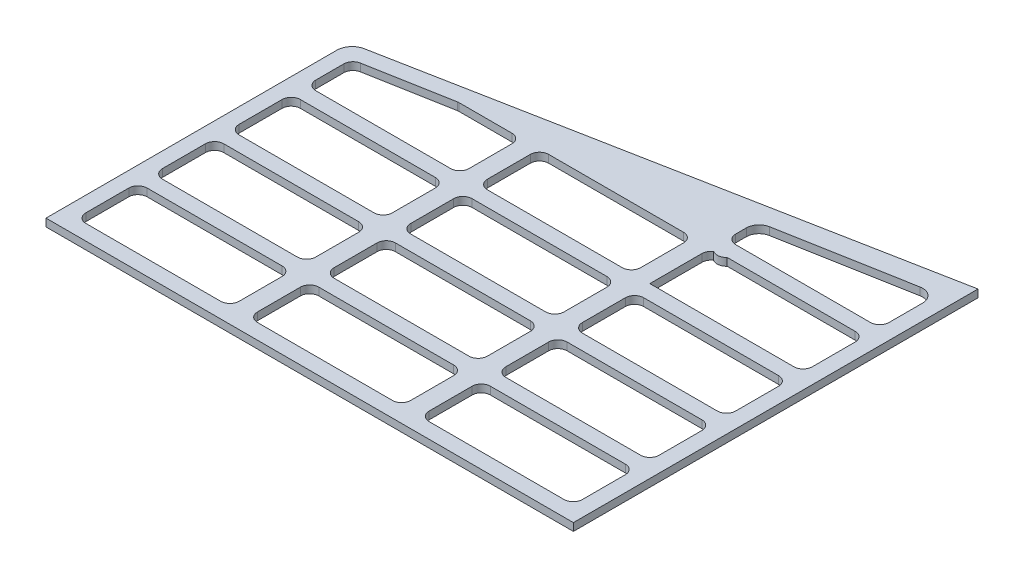
SolidWorks part; units mm, degrees
material "Balsa"
ref_plane "Front Plane" through (0, 0, 0) normal (0, 0, 1) x (1, 0, 0)
ref_plane "Top Plane" through (0, 0, 0) normal (0, 1, 0) x (1, 0, 0)
ref_plane "Right Plane" through (0, 0, 0) normal (1, 0, 0) x (0, 0, -1)
sketch "Sketch1" plane through (0, 0, 0) normal (0, 1, 0) x (1, 0, 0)
  line L0 (0, 0) -> (437.0222, 0)
  line L1 (437.0222, 335.28) -> (10.3078, 253.437)
  line L2 (0, 240.9644) -> (0, 0)
  line L3 (437.0222, 0) -> (437.0222, 335.28)
  arc A0 (10.3078, 253.437) -> (0, 240.9644) centre (12.7, 240.9644) ccw
  point P7 (0, 251.46)
  dimension "D4" = 12.7
  dimension "D1" = 251.46
  dimension "D2" = 437.0222
  dimension "D3" = 335.28
extrude "Boss-Extrude1" add sketch "Sketch1" along normal blind 6.35
sketch "Sketch2" plane through (0, 6.35, 0) normal (0, 1, 0) x (1, 0, 0)
  line L0 (0, 0) -> (437.0222, 0) construction
  line L1 (20.32, 12.7) -> (132.08, 12.7)
  line L2 (12.7, 20.32) -> (12.7, 55.88)
  line L3 (20.32, 63.5) -> (132.08, 63.5)
  line L4 (139.7, 20.32) -> (139.7, 55.88)
  line L5 (0, 240.9644) -> (0, 0) construction
  line L6 (154.94, 20.32) -> (154.94, 55.88)
  line L7 (162.56, 12.7) -> (274.32, 12.7)
  line L8 (281.94, 20.32) -> (281.94, 55.88)
  line L9 (162.56, 63.5) -> (274.32, 63.5)
  line L10 (297.18, 20.32) -> (297.18, 55.88)
  line L11 (304.8, 12.7) -> (416.56, 12.7)
  line L12 (424.18, 20.32) -> (424.18, 55.88)
  line L13 (304.8, 63.5) -> (416.56, 63.5)
  line L14 (154.94, 83.82) -> (154.94, 119.38)
  line L15 (162.56, 76.2) -> (274.32, 76.2)
  line L16 (281.94, 83.82) -> (281.94, 119.38)
  line L17 (162.56, 127) -> (274.32, 127)
  line L18 (297.18, 83.82) -> (297.18, 119.38)
  line L19 (304.8, 76.2) -> (416.56, 76.2)
  line L20 (424.18, 83.82) -> (424.18, 119.38)
  line L21 (304.8, 127) -> (416.56, 127)
  line L22 (154.94, 147.32) -> (154.94, 182.88)
  line L23 (162.56, 139.7) -> (274.32, 139.7)
  line L24 (281.94, 147.32) -> (281.94, 182.88)
  line L25 (162.56, 190.5) -> (274.32, 190.5)
  line L26 (297.18, 147.32) -> (297.18, 182.88)
  line L27 (304.8, 139.7) -> (416.56, 139.7)
  line L28 (424.18, 147.32) -> (424.18, 182.88)
  line L29 (304.8, 190.5) -> (416.56, 190.5)
  line L30 (154.94, 210.82) -> (154.94, 246.38)
  line L31 (162.56, 203.2) -> (274.32, 203.2)
  line L32 (281.94, 210.82) -> (281.94, 246.38)
  line L33 (162.56, 254) -> (274.32, 254)
  line L34 (297.18, 203.2) -> (297.18, 246.38)
  line L35 (297.18, 203.2) -> (416.56, 203.2)
  line L36 (424.18, 210.82) -> (424.18, 246.38)
  line L37 (304.8, 254) -> (416.56, 254)
  line L39 (242.4582, 266.7) -> (274.32, 266.7)
  line L40 (281.94, 274.32) -> (281.94, 280.0963)
  line L42 (297.18, 274.32) -> (297.18, 283.103)
  line L43 (310.8336, 266.7) -> (413.1927, 266.7)
  line L44 (424.18, 274.32) -> (424.18, 302.2704)
  line L46 (12.7, 83.82) -> (12.7, 119.38)
  line L47 (20.32, 76.2) -> (132.08, 76.2)
  line L48 (139.7, 83.82) -> (139.7, 119.38)
  line L49 (20.32, 127) -> (132.08, 127)
  line L50 (12.7, 147.32) -> (12.7, 182.88)
  line L51 (20.32, 139.7) -> (132.08, 139.7)
  line L52 (139.7, 147.32) -> (139.7, 182.88)
  line L53 (20.32, 190.5) -> (132.08, 190.5)
  line L54 (12.7, 210.82) -> (12.7, 234.048)
  line L55 (20.32, 203.2) -> (132.08, 203.2)
  line L56 (139.7, 210.82) -> (139.7, 246.38)
  line L57 (88.3426, 254) -> (132.08, 254)
  line L62 (411.6457, 312.7366) -> (305.9194, 293.5692)
  line L63 (272.9607, 287.5941) -> (241.0989, 281.8178)
  line L64 (12.7, 317.5) -> (139.7, 317.5) [skipped]
  line L65 (139.7, 266.7) -> (139.7, 317.5) [skipped]
  line L66 (12.7, 266.7) -> (12.7, 317.5) [skipped]
  line L67 (12.7, 266.7) -> (139.7, 266.7) [skipped]
  line L68 (154.94, 266.7) -> (154.94, 317.5) [skipped]
  line L69 (154.94, 317.5) -> (281.94, 317.5) [skipped]
  line L70 (297.18, 317.5) -> (424.18, 317.5) [skipped]
  line L71 (86.9833, 253.8778) -> (18.9607, 241.5458)
  line L72 (310.8336, 266.7) -> (297.18, 266.7)
  line L73 (304.8, 266.7) -> (416.56, 266.7)
  arc A0 (241.0989, 281.8178) -> (242.4582, 266.7) centre (242.4582, 274.32) ccw
  arc A1 (281.94, 280.0963) -> (272.9607, 287.5941) centre (274.32, 280.0963) ccw
  arc A2 (274.32, 266.7) -> (281.94, 274.32) centre (274.32, 274.32) ccw
  arc A3 (132.08, 203.2) -> (139.7, 210.82) centre (132.08, 210.82) ccw
  arc A4 (139.7, 182.88) -> (132.08, 190.5) centre (132.08, 182.88) ccw
  arc A5 (132.08, 139.7) -> (139.7, 147.32) centre (132.08, 147.32) ccw
  arc A6 (139.7, 119.38) -> (132.08, 127) centre (132.08, 119.38) ccw
  arc A7 (132.08, 76.2) -> (139.7, 83.82) centre (132.08, 83.82) ccw
  arc A8 (132.08, 63.5) -> (139.7, 55.88) centre (132.08, 55.88) cw
  arc A9 (132.08, 12.7) -> (139.7, 20.32) centre (132.08, 20.32) ccw
  arc A10 (20.32, 12.7) -> (12.7, 20.32) centre (20.32, 20.32) cw
  arc A11 (12.7, 55.88) -> (20.32, 63.5) centre (20.32, 55.88) cw
  arc A12 (12.7, 83.82) -> (20.32, 76.2) centre (20.32, 83.82) ccw
  arc A13 (12.7, 119.38) -> (20.32, 127) centre (20.32, 119.38) cw
  arc A14 (12.7, 147.32) -> (20.32, 139.7) centre (20.32, 147.32) ccw
  arc A15 (12.7, 182.88) -> (20.32, 190.5) centre (20.32, 182.88) cw
  arc A16 (12.7, 210.82) -> (20.32, 203.2) centre (20.32, 210.82) ccw
  arc A17 (18.9607, 241.5458) -> (12.7, 234.048) centre (20.32, 234.048) ccw
  arc A18 (88.3426, 254) -> (86.9833, 253.8778) centre (88.3426, 246.38) ccw
  arc A19 (139.7, 246.38) -> (132.08, 254) centre (132.08, 246.38) ccw
  arc A20 (154.94, 246.38) -> (162.56, 254) centre (162.56, 246.38) cw
  arc A21 (154.94, 210.82) -> (162.56, 203.2) centre (162.56, 210.82) ccw
  arc A22 (154.94, 182.88) -> (162.56, 190.5) centre (162.56, 182.88) cw
  arc A23 (154.94, 147.32) -> (162.56, 139.7) centre (162.56, 147.32) ccw
  arc A24 (154.94, 119.38) -> (162.56, 127) centre (162.56, 119.38) cw
  arc A25 (154.94, 83.82) -> (162.56, 76.2) centre (162.56, 83.82) ccw
  arc A26 (154.94, 55.88) -> (162.56, 63.5) centre (162.56, 55.88) cw
  arc A27 (154.94, 20.32) -> (162.56, 12.7) centre (162.56, 20.32) ccw
  arc A28 (274.32, 12.7) -> (281.94, 20.32) centre (274.32, 20.32) ccw
  arc A29 (281.94, 55.88) -> (274.32, 63.5) centre (274.32, 55.88) ccw
  arc A30 (274.32, 76.2) -> (281.94, 83.82) centre (274.32, 83.82) ccw
  arc A31 (281.94, 119.38) -> (274.32, 127) centre (274.32, 119.38) ccw
  arc A32 (274.32, 139.7) -> (281.94, 147.32) centre (274.32, 147.32) ccw
  arc A33 (281.94, 182.88) -> (274.32, 190.5) centre (274.32, 182.88) ccw
  arc A34 (274.32, 203.2) -> (281.94, 210.82) centre (274.32, 210.82) ccw
  arc A35 (281.94, 246.38) -> (274.32, 254) centre (274.32, 246.38) ccw
  arc A36 (297.18, 182.88) -> (304.8, 190.5) centre (304.8, 182.88) cw
  arc A37 (297.18, 147.32) -> (304.8, 139.7) centre (304.8, 147.32) ccw
  arc A38 (297.18, 119.38) -> (304.8, 127) centre (304.8, 119.38) cw
  arc A39 (297.18, 83.82) -> (304.8, 76.2) centre (304.8, 83.82) ccw
  arc A40 (297.18, 55.88) -> (304.8, 63.5) centre (304.8, 55.88) cw
  arc A41 (297.18, 20.32) -> (304.8, 12.7) centre (304.8, 20.32) ccw
  arc A42 (416.56, 12.7) -> (424.18, 20.32) centre (416.56, 20.32) ccw
  arc A43 (424.18, 55.88) -> (416.56, 63.5) centre (416.56, 55.88) ccw
  arc A44 (416.56, 76.2) -> (424.18, 83.82) centre (416.56, 83.82) ccw
  arc A45 (424.18, 119.38) -> (416.56, 127) centre (416.56, 119.38) ccw
  arc A46 (416.56, 139.7) -> (424.18, 147.32) centre (416.56, 147.32) ccw
  arc A47 (424.18, 182.88) -> (416.56, 190.5) centre (416.56, 182.88) ccw
  arc A48 (416.56, 203.2) -> (424.18, 210.82) centre (416.56, 210.82) ccw
  arc A49 (424.18, 246.38) -> (416.56, 254) centre (416.56, 246.38) ccw
  arc A50 (297.18, 246.38) -> (304.8, 254) centre (304.8, 246.38) cw
  arc A51 (300.5879, 252.73) -> (310.4796, 254) centre (304.8, 259.08) ccw
  arc A53 (424.18, 302.2704) -> (411.6457, 312.7366) centre (413.5432, 302.2704) ccw
  arc A54 (305.9194, 293.5692) -> (297.18, 283.103) centre (307.8168, 283.103) ccw
  arc A55 (416.56, 266.7) -> (424.18, 274.32) centre (416.56, 274.32) ccw
  arc A56 (297.18, 274.32) -> (304.8, 266.7) centre (304.8, 274.32) ccw
  point P64 (281.94, 289.222)
  point P93 (139.7, 63.5)
  point P96 (139.7, 12.7)
  point P101 (12.7, 63.5)
  point P194 (0, 0)
  dimension "D7" = 7.62
  dimension "D8" = 7.62
  dimension "D1" = 127
  dimension "D2" = 50.8
  dimension "D3" = 12.7
  dimension "D4" = 12.7
  dimension "D5" = 3
  dimension "D6" = 5
extrude "Cut-Extrude1" cut sketch "Sketch2" against normal up to surface (6.35 mm away) contours L42 A56 L72 L43 L73 A55 L44 A53 L62 A54 | A51 A50 L34 L35 A48 L36 A49 L37 | L32 A35 L33 A20 L30 A21 L31 A34 | L24 A33 L25 A22 L22 A23 L23 A32 | L28 A47 L29 A36 L26 A37 L27 A46 | L20 A45 L21 A38 L18 A39 L19 A44 | L16 A31 L17 A24 L14 A25 L15 A30 | L8 A29 L9 A26 L6 A27 L7 A28 | L12 A43 L13 A40 L10 A41 L11 A42 | A15 L50 A14 L51 A5 L52 A4 L53 | A13 L46 A12 L47 A7 L48 A6 L49 | A11 L2 A10 L1 A9 L4 A8 L3 | L56 A19 L57 A18 L71 A17 L54 A16 L55 A3 region at (76.2, 6.35, -38.1) region at (218.44, 6.35, -38.1) region at (360.68, 6.35, -38.1) region at (218.44, 6.35, -101.6) region at (360.68, 6.35, -101.6) region at (218.44, 6.35, -165.1) region at (360.68, 6.35, -165.1) region at (218.44, 6.35, -228.6) region at (360.7087, 6.35, -228.4884) region at (367.1432, 6.35, -285.5711) region at (76.2, 6.35, -101.6) region at (76.2, 6.35, -165.1) region at (79.4811, 6.35, -226.8328) up to face at (176.4218, 0, -166.3071)
